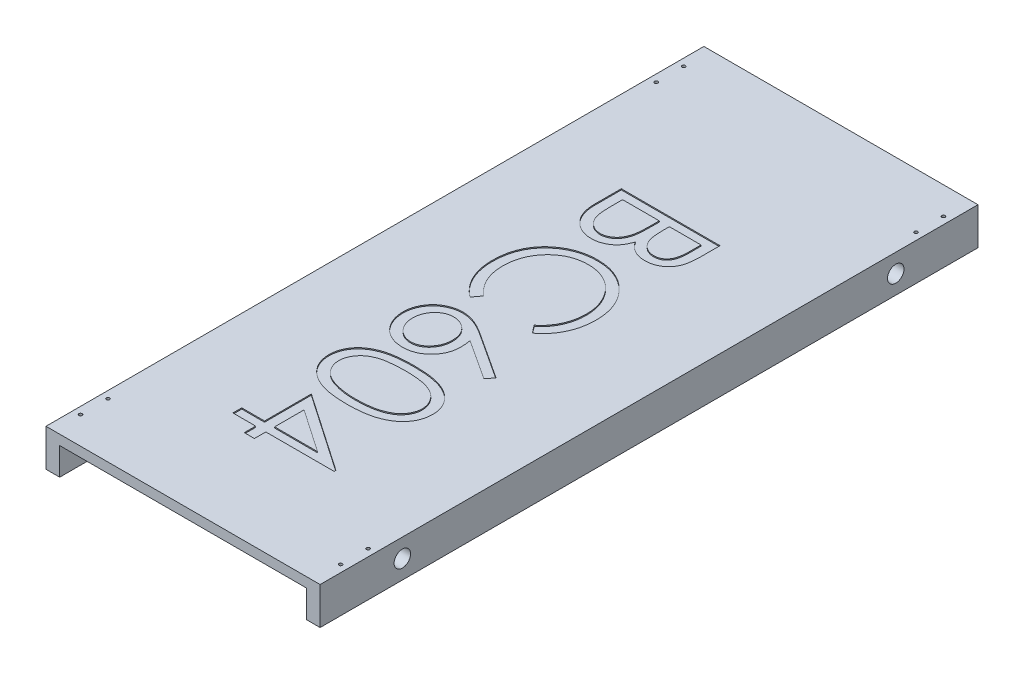
SolidWorks part; units mm, degrees
ref_plane "Front Plane" through (0, 0, 0) normal (0, 0, 1) x (1, 0, 0)
ref_plane "Top Plane" through (0, 0, 0) normal (0, 1, 0) x (1, 0, 0)
ref_plane "Right Plane" through (0, 0, 0) normal (1, 0, 0) x (0, 0, -1)
sketch "Sketch2" plane through (0, 0, 0) normal (0, 0, 1) x (1, 0, 0)
  line L1 (-251.2821, 174.5411) -> (248.7179, 174.5411)
  line L2 (-251.2821, 174.5411) -> (-251.2821, 156.5411)
  line L3 (-226.2821, 156.5411) -> (223.7179, 156.5411)
  line L4 (248.7179, 174.5411) -> (248.7179, 156.5411)
  line L6 (-251.2821, 156.5411) -> (-251.2821, 106.5411)
  line L7 (-251.2821, 106.5411) -> (-226.2821, 106.5411)
  line L8 (-226.2821, 156.5411) -> (-226.2821, 106.5411)
  line L10 (248.7179, 156.5411) -> (248.7179, 106.5411)
  line L11 (248.7179, 106.5411) -> (223.7179, 106.5411)
  line L12 (223.7179, 156.5411) -> (223.7179, 106.5411)
  dimension "D1" = 500
  dimension "D2" = 18
  dimension "D3" = 25
  dimension "D4" = 50
  dimension "D5" = 25
  dimension "D6" = 50
extrude "Boss-Extrude1" add sketch "Sketch2" along normal blind 1200 contours L3 L12 L11 L10 L4 L1 L2 L6 L7 L8
sketch "Sketch4" plane through (0, 0, 0) normal (1, 0, 0) x (0, 0, -1)
  line L0 (-600, 174.5411) -> (-600, 106.5411)
  line L2 (-1200, 174.5411) -> (0, 174.5411) construction
  line L3 (-1200, 106.5411) -> (0, 106.5411) construction
  circle A0 centre (-1050, 140.5411) radius 15
  circle A1 centre (-150, 140.5411) radius 15
  dimension "D1" = 30
extrude "Cut-Extrude1" cut sketch "Sketch4" against normal through all both and the other way through all contours A0
extrude "Cut-Extrude2" cut sketch "Sketch4<3>" against normal through all and the other way through all contours A1
sketch "Sketch4<3>" plane through (0, 0, 0) normal (1, 0, 0) x (0, 0, -1) same geometry as "Sketch4"
sketch "Sketch9" plane through (0, 174.5411, 0) normal (0, 1, 0) x (1, 0, 0)
  line L0 (-101.8538, -276.968) -> (-101.8538, -1001.968)
  line L1 (-94.5452, -1001.968) -> (-94.5452, -276.968)
  line L2 (-94.5452, -276.968) -> (-94.5452, -1001.968)
sketch "Sketch10" plane through (0, 174.5411, 0) normal (0, 1, 0) x (1, 0, 0)
  text T0 "BC604" font "Century Gothic" height 180
extrude "Cut-Extrude3" cut sketch "Sketch10" against normal blind 2
sketch "Sketch12" plane through (0, 156.5411, 0) normal (0, -1, 0) x (-1, 0, 0)
  text T0 "BC604" font "Century Gothic" height 180
extrude "Cut-Extrude4" cut sketch "Sketch12" against normal blind 2
hole_wizard "Ø6.0 (6) Diameter Hole1" positions "Sketch13" profile "Sketch14" hole size "Ø6.0" standard "ISO" end condition through all
sketch "Sketch13" plane through (0, 156.5411, 0) normal (0, -1, 0) x (-1, 0, 0)
  line L0 (-248.7179, 0) -> (-235.7179, 0)
  line L1 (-248.7179, 0) -> (-223.7179, 0) construction
  line L2 (-235.7179, 0) -> (-235.7179, -50)
  line L3 (-235.7179, -50) -> (-235.7179, -100)
  line L4 (-248.7179, -1200) -> (-235.7179, -1200)
  line L5 (-248.7179, -1200) -> (-223.7179, -1200) construction
  line L6 (-235.7179, -1200) -> (-235.7179, -1199.5571)
  line L7 (-235.7179, -1199.5571) -> (-235.7179, -1149.5571)
  line L9 (-235.7179, -1149.5571) -> (-235.7179, -1099.5571)
  line L11 (251.2821, -1200) -> (238.2821, -1200)
  line L12 (251.2821, -1200) -> (226.2821, -1200) construction
  line L14 (238.2821, -1200) -> (238.2821, -1150)
  line L16 (238.2821, -1150) -> (238.2821, -1100)
  line L18 (251.2821, 0) -> (238.2821, 0)
  line L19 (251.2821, 0) -> (226.2821, 0) construction
  line L20 (238.2821, 0) -> (238.2821, -50)
  line L21 (238.2821, -50) -> (238.2821, -100)
  point P6 (-235.7179, -50)
  point P8 (-235.7179, -100)
  point P26 (-235.7179, -1149.5571)
  point P30 (-235.7179, -1099.5571)
  point P44 (238.2821, -1150)
  point P51 (238.2821, -1100)
  point P60 (238.2821, -50)
  point P62 (238.2821, -100)
  dimension "D1" = 13
  dimension "D2" = 50
  dimension "D3" = 50
  dimension "D4" = 13
  dimension "D5" = 50
  dimension "D6" = 50
  dimension "D7" = 13
  dimension "D8" = 50
  dimension "D9" = 50
  dimension "D10" = 13
  dimension "D11" = 50
  dimension "D12" = 50
sketch "Sketch14" plane through (-238.2821, 156.5411, 100) normal (1, 0, 0) x (0, 0, -1)
  line L0 (0, 0) -> (0, 18)
  line L1 (0, 18) -> (3, 18)
  line L2 (3, 18) -> (3, 0.025)
  line L3 (3, 0.025) -> (3.025, 0)
  line L5 (3.025, 0) -> (0, 0)
  line L6 (-3, 0.025) -> (-3.025, 0) construction
  line L11 (0, -6.35) -> (0, 107.95) construction
  dimension "Thru Hole Dia." = 6
  dimension "Thru Hole Depth" = 18
  dimension "Near C'Sink Dia." = 6.05
  dimension "Near C'Sink Angle" = 90
